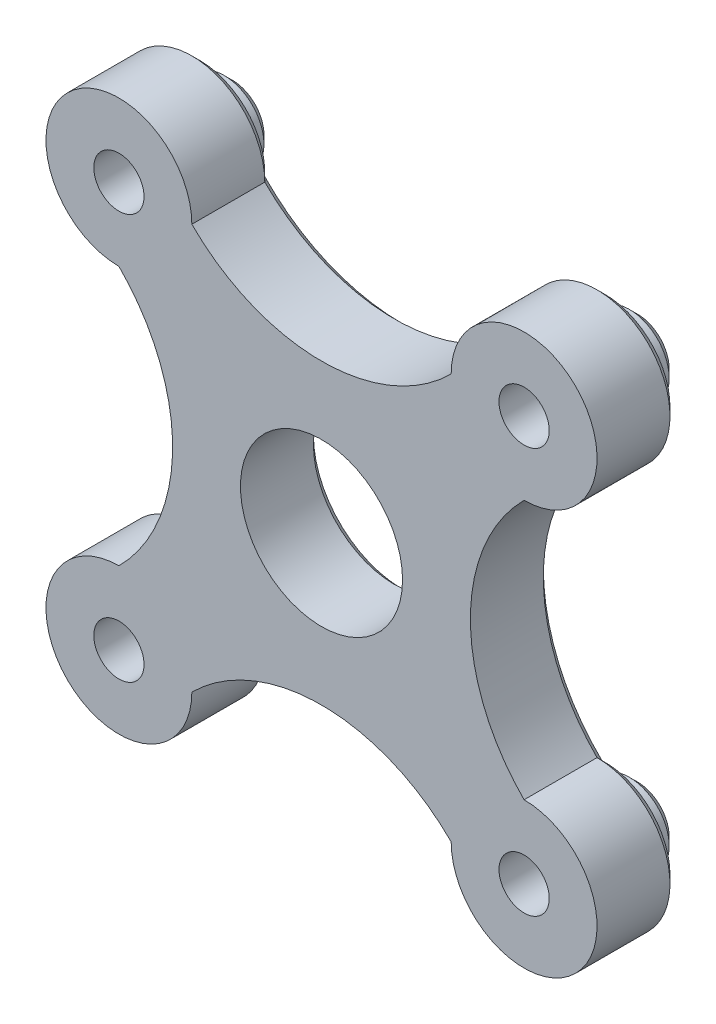
SolidWorks part; units mm, degrees
ref_plane "Alzado" through (0, 0, 0) normal (0, 0, 1) x (1, 0, 0)
ref_plane "Planta" through (0, 0, 0) normal (0, 1, 0) x (1, 0, 0)
ref_plane "Vista lateral" through (0, 0, 0) normal (1, 0, 0) x (0, 0, -1)
sketch "Croquis1" plane through (0, 0, 0) normal (0, 0, 1) x (1, 0, 0)
  line L1 (12.5, 12.5) -> (-12.5, 12.5)
  line L2 (12.5, 12.5) -> (12.5, -12.5)
  line L3 (12.5, -12.5) -> (-12.5, -12.5)
  line L4 (-12.5, 12.5) -> (-12.5, -12.5)
  line L5 (12.5, 12.5) -> (-12.5, -12.5) construction
  line L6 (12.5, -12.5) -> (-12.5, 12.5) construction
  circle A0 centre (-12.5, 12.5) radius 2.45
  circle A1 centre (12.5, 12.5) radius 2.45
  circle A2 centre (12.5, -12.5) radius 2.45
  circle A3 centre (-12.5, -12.5) radius 2.45
  point P0 (0, 0)
  dimension "D3" = 4.9
  dimension "D1" = 25
  dimension "D2" = 25
  dimension "D4" = 2
  dimension "D5" = 2
extrude "Saliente-Extruir1" add sketch "Croquis1" along normal blind 2 contours L4 A3 L3 | L3 A2 L2 | L2 A2 L3 | L3 A3 L4 | L4 A0 L1 | A0 | A1 region at (-11.4602, 11.4602, 0) region at (-11.4602, -11.4602, 0) region at (-12.8466, -12.8466, 0) region at (12.8466, -12.8466, 0) region at (11.4602, -11.4602, 0)
sketch "Croquis2" plane through (0, 0, 2) normal (0, 0, 1) x (1, 0, 0)
  arc A0 (-8, 12.5) -> (-12.5, 8) centre (-12.5, 12.5) ccw
  arc A1 (12.5, 8) -> (8, 12.5) centre (12.5, 12.5) ccw
  arc A2 (8, -12.5) -> (12.5, -8) centre (12.5, -12.5) ccw
  arc A3 (-12.5, -8) -> (-8, -12.5) centre (-12.5, -12.5) ccw
  arc A4 (-12.5, 8) -> (-12.5, -8) centre (-20.5, 0) cw
  arc A5 (8, 12.5) -> (-8, 12.5) centre (0, 20.5) cw
  arc A6 (12.5, -8) -> (12.5, 8) centre (20.5, 0) cw
  arc A7 (-8, -12.5) -> (8, -12.5) centre (0, -20.5) cw
  point P24 (0, 0)
  dimension "D1" = 9
  dimension "D2" = 2
  dimension "D3" = 2
  dimension "D4" = 4
extrude "Saliente-Extruir2" add sketch "Croquis2" along normal blind 5
sketch "Croquis3" plane through (0, 0, 0) normal (0, 0, -1) x (-1, 0, 0)
  circle A0 centre (-12.5, -12.5) radius 1.55
  circle A1 centre (12.5, -12.5) radius 1.55
  circle A2 centre (12.5, 12.5) radius 1.55
  circle A3 centre (-12.5, 12.5) radius 1.55
  dimension "D1" = 3.1
  dimension "D2" = 2
  dimension "D3" = 2
extrude "Cortar-Extruir1" cut sketch "Croquis3" against normal through all
sketch "Croquis4" plane through (0, 0, 7) normal (0, 0, 1) x (1, 0, 0)
  circle A0 centre (0, 0) radius 5
  dimension "D1" = 10
extrude "Cortar-Extruir2" cut sketch "Croquis4" against normal blind 5
chamfer "Chaflán1" distance 0.5 angle 45 4 edges at (-10.05, 12.5, 0) (14.95, 12.5, 0) (14.95, -12.5, 0) (-10.05, -12.5, 0)
chamfer "Chaflán2" distance 0.5 angle 45 9 edges at (5, 0, 2) (0, -9.1863, 2) (15.682, -15.682, 2) (9.1863, 0, 2) (15.682, 15.682, 2) (0, 9.1863, 2) (-15.682, 15.682, 2) (-9.1863, 0, 2) (-15.682, -15.682, 2)
